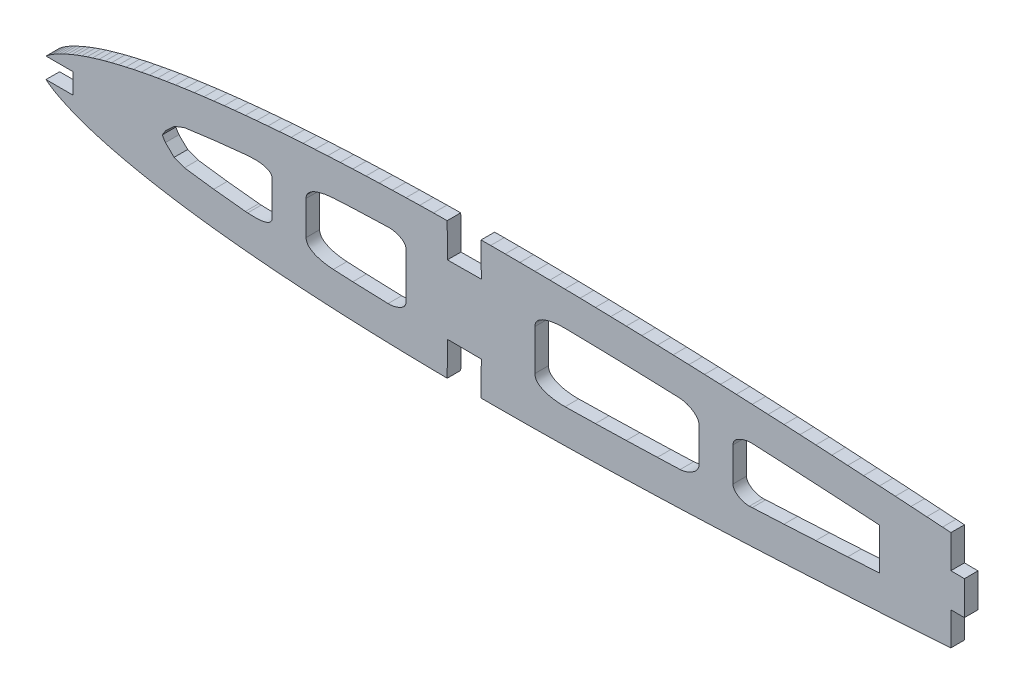
SolidWorks part; units mm, degrees
ref_plane "前视基准面" through (0, 0, 0) normal (0, 0, 1) x (1, 0, 0)
ref_plane "上视基准面" through (0, 0, 0) normal (0, 1, 0) x (1, 0, 0)
ref_plane "右视基准面" through (0, 0, 0) normal (1, 0, 0) x (0, 0, -1)
sketch "Model" plane through (0, 0, 0) normal (0, 0, 1) x (1, 0, 0)
  line L0 (21.4573, -121.0987) -> (25.4497, -121.0987)
  line L1 (25.4497, -121.0987) -> (25.4497, -124.0987)
  line L2 (25.4497, -124.0987) -> (21.4569, -124.0987)
  line L3 (85.6707, -112.4927) -> (85.7057, -117.4927)
  line L4 (85.7057, -117.4927) -> (80.7057, -117.5247)
  line L5 (80.7057, -117.5247) -> (80.6707, -112.5256)
  line L6 (85.6707, -132.7057) -> (85.7037, -127.7057)
  line L7 (85.7037, -127.7057) -> (80.7037, -127.6737)
  line L8 (80.7037, -127.6737) -> (80.6707, -132.6727)
  line L9 (155.0158, -115.2299) -> (153.7727, -115.1437)
  line L10 (153.7727, -115.1437) -> (151.4507, -114.9857)
  line L11 (151.4507, -114.9857) -> (149.1287, -114.8307)
  line L12 (149.1287, -114.8307) -> (146.8067, -114.6807)
  line L13 (146.8067, -114.6807) -> (144.4647, -114.5347)
  line L14 (144.4647, -114.5347) -> (142.1237, -114.3927)
  line L15 (142.1237, -114.3927) -> (139.7817, -114.2547)
  line L16 (139.7817, -114.2547) -> (137.4317, -114.1167)
  line L17 (137.4317, -114.1167) -> (135.0827, -113.9827)
  line L18 (135.0827, -113.9827) -> (132.7327, -113.8527)
  line L19 (132.7327, -113.8527) -> (130.3827, -113.7277)
  line L20 (130.3827, -113.7277) -> (128.0337, -113.6087)
  line L21 (128.0337, -113.6087) -> (125.6837, -113.4957)
  line L22 (125.6837, -113.4957) -> (123.3417, -113.3877)
  line L23 (123.3417, -113.3877) -> (121.0007, -113.2847)
  line L24 (121.0007, -113.2847) -> (118.6587, -113.1877)
  line L25 (118.6587, -113.1877) -> (116.3367, -113.0957)
  line L26 (116.3367, -113.0957) -> (114.0157, -113.0097)
  line L27 (114.0157, -113.0097) -> (111.6927, -112.9297)
  line L28 (111.6927, -112.9297) -> (109.3977, -112.8557)
  line L29 (109.3977, -112.8557) -> (107.1037, -112.7887)
  line L30 (107.1037, -112.7887) -> (104.8077, -112.7277)
  line L31 (104.8077, -112.7277) -> (102.5507, -112.6727)
  line L32 (102.5507, -112.6727) -> (100.2927, -112.6247)
  line L33 (100.2927, -112.6247) -> (98.0347, -112.5837)
  line L34 (98.0347, -112.5837) -> (95.8227, -112.5497)
  line L35 (95.8227, -112.5497) -> (93.6117, -112.5237)
  line L36 (93.6117, -112.5237) -> (91.3997, -112.5047)
  line L37 (91.3997, -112.5047) -> (89.2407, -112.4937)
  line L38 (89.2407, -112.4937) -> (87.0837, -112.4897)
  line L39 (87.0837, -112.4897) -> (85.6707, -112.4927)
  line L40 (41.8937, -120.0317) -> (46.2167, -119.4607)
  line L41 (46.2167, -119.4607) -> (50.8827, -118.9597)
  line L42 (50.8827, -118.9597) -> (51.3585, -118.9186)
  line L43 (63.9417, -118.0316) -> (64.3393, -118.0115)
  line L44 (66.7357, -117.8907) -> (71.9805, -117.7055)
  line L45 (74.5927, -119.2019) -> (74.5927, -124.3091)
  line L46 (71.9424, -127.4906) -> (66.7357, -127.3067)
  line L47 (66.7357, -127.3067) -> (63.8661, -127.1621)
  line L48 (51.2155, -126.2665) -> (50.8827, -126.2377)
  line L49 (50.8827, -126.2377) -> (46.2167, -125.7367)
  line L50 (46.2167, -125.7367) -> (41.8937, -125.1657)
  line L51 (98.0347, -117.5837) -> (101.1763, -117.6456)
  line L52 (103.8714, -117.7064) -> (107.1037, -117.7887)
  line L53 (107.1037, -117.7887) -> (111.6927, -117.9297)
  line L54 (111.6927, -117.9297) -> (114.9886, -118.0475)
  line L55 (125.6837, -118.4957) -> (130.3827, -118.7277)
  line L56 (130.3827, -118.7277) -> (135.0827, -118.9827)
  line L57 (135.0827, -118.9827) -> (139.7817, -119.2547)
  line L58 (139.7817, -119.2547) -> (144.4647, -119.5347)
  line L59 (144.4647, -125.6627) -> (139.7817, -125.9427)
  line L60 (139.7817, -125.9427) -> (135.0827, -126.2147)
  line L61 (135.0827, -126.2147) -> (130.3827, -126.4697)
  line L62 (130.3827, -126.4697) -> (125.6837, -126.7017)
  line L63 (125.6837, -126.7017) -> (125.2777, -126.72)
  line L64 (115.0535, -127.1476) -> (111.6927, -127.2677)
  line L65 (111.6927, -127.2677) -> (107.1037, -127.4087)
  line L66 (107.1037, -127.4087) -> (102.5507, -127.5247)
  line L67 (102.5507, -127.5247) -> (98.0702, -127.613)
  line L68 (41.8937, -120.0317) -> (40.3728, -120.6165)
  line L69 (40.3728, -120.6165) -> (39.0836, -121.8522)
  line L70 (39.0836, -121.8522) -> (38.6143, -122.5987)
  line L71 (41.8937, -125.1657) -> (40.3728, -124.581)
  line L72 (40.3728, -124.581) -> (39.0836, -123.3453)
  line L73 (39.0836, -123.3453) -> (38.6143, -122.5987)
  line L74 (74.5927, -119.2019) -> (74.5927, -125.9956)
  line L75 (93.6117, -119.5956) -> (93.6117, -125.6018)
  line L76 (59.8455, -120.0987) -> (59.8455, -125.0987)
  line L77 (54.8455, -125.0987) -> (54.8455, -120.0987)
  line L78 (122.8505, -120.0987) -> (122.8505, -125.0987)
  line L79 (117.8505, -125.0987) -> (117.8505, -120.0987)
  line L80 (157.0157, -122.5981) -> (157.0157, -120.0981)
  line L81 (157.0157, -122.5981) -> (157.0157, -125.0981)
  line L82 (157.0157, -120.1177) -> (155.0158, -120.0981)
  line L83 (157.0157, -125.0981) -> (155.0157, -125.0981)
  line L84 (155.0157, -125.0981) -> (155.0157, -129.9686)
  line L85 (155.0158, -120.0981) -> (155.0158, -115.2299)
  line L86 (144.4647, -119.5347) -> (144.4647, -125.6627)
  line L87 (101.1763, -117.6456) -> (103.8714, -117.7064)
  line L88 (64.3393, -118.0115) -> (66.7357, -117.8907)
  line L89 (80.6707, -112.5256) -> (78.6397, -112.5517)
  line L90 (78.6397, -112.5517) -> (76.6157, -112.5877)
  line L91 (76.6157, -112.5877) -> (74.5927, -112.6317)
  line L92 (74.5927, -112.6317) -> (72.5697, -112.6847)
  line L93 (72.5697, -112.6847) -> (70.6237, -112.7447)
  line L94 (70.6237, -112.7447) -> (68.6797, -112.8127)
  line L95 (68.6797, -112.8127) -> (66.7357, -112.8907)
  line L96 (66.7357, -112.8907) -> (64.8767, -112.9747)
  line L97 (64.8767, -112.9747) -> (63.0187, -113.0687)
  line L98 (63.0187, -113.0687) -> (61.1617, -113.1717)
  line L99 (61.1617, -113.1717) -> (59.3967, -113.2807)
  line L100 (59.3967, -113.2807) -> (57.6337, -113.3987)
  line L101 (57.6337, -113.3987) -> (55.8707, -113.5287)
  line L102 (55.8707, -113.5287) -> (54.2067, -113.6617)
  line L103 (54.2067, -113.6617) -> (52.5447, -113.8057)
  line L104 (52.5447, -113.8057) -> (50.8827, -113.9597)
  line L105 (50.8827, -113.9597) -> (49.3267, -114.1157)
  line L106 (49.3267, -114.1157) -> (47.7707, -114.2817)
  line L107 (47.7707, -114.2817) -> (46.2167, -114.4607)
  line L108 (46.2167, -114.4607) -> (44.7737, -114.6387)
  line L109 (44.7737, -114.6387) -> (43.3337, -114.8287)
  line L110 (43.3337, -114.8287) -> (41.8937, -115.0317)
  line L111 (41.8937, -115.0317) -> (40.5707, -115.2307)
  line L112 (40.5707, -115.2307) -> (39.2497, -115.4417)
  line L113 (39.2497, -115.4417) -> (37.9307, -115.6667)
  line L114 (37.9307, -115.6667) -> (36.7307, -115.8847)
  line L115 (36.7307, -115.8847) -> (35.5337, -116.1147)
  line L116 (35.5337, -116.1147) -> (34.3397, -116.3607)
  line L117 (34.3397, -116.3607) -> (33.2687, -116.5957)
  line L118 (33.2687, -116.5957) -> (32.2007, -116.8447)
  line L119 (32.2007, -116.8447) -> (31.1367, -117.1087)
  line L120 (31.1367, -117.1087) -> (30.1987, -117.3557)
  line L121 (30.1987, -117.3557) -> (29.2647, -117.6177)
  line L122 (29.2647, -117.6177) -> (28.3347, -117.8967)
  line L123 (28.3347, -117.8967) -> (27.5317, -118.1547)
  line L124 (27.5317, -118.1547) -> (26.7347, -118.4287)
  line L125 (26.7347, -118.4287) -> (25.9447, -118.7227)
  line L126 (25.9447, -118.7227) -> (25.2827, -118.9887)
  line L127 (25.2827, -118.9887) -> (24.6267, -119.2697)
  line L128 (24.6267, -119.2697) -> (23.9777, -119.5677)
  line L129 (23.9777, -119.5677) -> (23.4557, -119.8227)
  line L130 (23.4557, -119.8227) -> (22.9417, -120.0947)
  line L131 (22.9417, -120.0947) -> (22.4397, -120.3897)
  line L132 (22.4397, -120.3897) -> (22.0567, -120.6397)
  line L133 (22.0567, -120.6397) -> (21.6867, -120.9097)
  line L134 (21.6867, -120.9097) -> (21.4573, -121.0987)
  line L135 (85.6707, -132.7057) -> (87.0837, -132.7087)
  line L136 (87.0837, -132.7087) -> (89.2407, -132.7047)
  line L137 (89.2407, -132.7047) -> (91.3997, -132.6937)
  line L138 (91.3997, -132.6937) -> (93.6117, -132.6747)
  line L139 (93.6117, -132.6747) -> (95.8227, -132.6477)
  line L140 (95.8227, -132.6477) -> (98.0347, -132.6147)
  line L141 (98.0347, -132.6147) -> (100.2927, -132.5737)
  line L142 (100.2927, -132.5737) -> (102.5507, -132.5257)
  line L143 (102.5507, -132.5257) -> (104.8077, -132.4707)
  line L144 (104.8077, -132.4707) -> (107.1037, -132.4097)
  line L145 (107.1037, -132.4097) -> (109.3977, -132.3427)
  line L146 (109.3977, -132.3427) -> (111.6927, -132.2687)
  line L147 (111.6927, -132.2687) -> (114.0157, -132.1887)
  line L148 (114.0157, -132.1887) -> (116.3367, -132.1027)
  line L149 (116.3367, -132.1027) -> (118.6587, -132.0107)
  line L150 (118.6587, -132.0107) -> (121.0007, -131.9137)
  line L151 (121.0007, -131.9137) -> (123.3417, -131.8107)
  line L152 (123.3417, -131.8107) -> (125.6837, -131.7027)
  line L153 (125.6837, -131.7027) -> (128.0337, -131.5897)
  line L154 (128.0337, -131.5897) -> (130.3827, -131.4707)
  line L155 (130.3827, -131.4707) -> (132.7327, -131.3457)
  line L156 (132.7327, -131.3457) -> (135.0827, -131.2157)
  line L157 (135.0827, -131.2157) -> (137.4317, -131.0817)
  line L158 (137.4317, -131.0817) -> (139.7817, -130.9437)
  line L159 (139.7817, -130.9437) -> (142.1237, -130.8047)
  line L160 (142.1237, -130.8047) -> (144.4647, -130.6637)
  line L161 (144.4647, -130.6637) -> (146.8067, -130.5177)
  line L162 (146.8067, -130.5177) -> (149.1287, -130.3677)
  line L163 (149.1287, -130.3677) -> (151.4507, -130.2127)
  line L164 (151.4507, -130.2127) -> (153.7727, -130.0547)
  line L165 (153.7727, -130.0547) -> (155.0157, -129.9686)
  line L166 (21.4569, -124.0987) -> (21.6867, -124.2887)
  line L167 (21.6867, -124.2887) -> (22.0567, -124.5587)
  line L168 (22.0567, -124.5587) -> (22.4397, -124.8087)
  line L169 (22.4397, -124.8087) -> (22.9417, -125.1037)
  line L170 (22.9417, -125.1037) -> (23.4557, -125.3757)
  line L171 (23.4557, -125.3757) -> (23.9777, -125.6307)
  line L172 (23.9777, -125.6307) -> (24.6267, -125.9287)
  line L173 (24.6267, -125.9287) -> (25.2827, -126.2097)
  line L174 (25.2827, -126.2097) -> (25.9447, -126.4747)
  line L175 (25.9447, -126.4747) -> (26.7347, -126.7687)
  line L176 (26.7347, -126.7687) -> (27.5317, -127.0437)
  line L177 (27.5317, -127.0437) -> (28.3347, -127.3017)
  line L178 (28.3347, -127.3017) -> (29.2647, -127.5807)
  line L179 (29.2647, -127.5807) -> (30.1987, -127.8427)
  line L180 (30.1987, -127.8427) -> (31.1367, -128.0897)
  line L181 (31.1367, -128.0897) -> (32.2007, -128.3537)
  line L182 (32.2007, -128.3537) -> (33.2687, -128.6027)
  line L183 (33.2687, -128.6027) -> (34.3397, -128.8377)
  line L184 (34.3397, -128.8377) -> (35.5337, -129.0837)
  line L185 (35.5337, -129.0837) -> (36.7307, -129.3137)
  line L186 (36.7307, -129.3137) -> (37.9307, -129.5317)
  line L187 (37.9307, -129.5317) -> (39.2497, -129.7567)
  line L188 (39.2497, -129.7567) -> (40.5707, -129.9677)
  line L189 (40.5707, -129.9677) -> (41.8937, -130.1667)
  line L190 (41.8937, -130.1667) -> (43.3337, -130.3697)
  line L191 (43.3337, -130.3697) -> (44.7737, -130.5597)
  line L192 (44.7737, -130.5597) -> (46.2167, -130.7377)
  line L193 (46.2167, -130.7377) -> (47.7707, -130.9157)
  line L194 (47.7707, -130.9157) -> (49.3267, -131.0827)
  line L195 (49.3267, -131.0827) -> (50.8827, -131.2377)
  line L196 (50.8827, -131.2377) -> (52.5447, -131.3927)
  line L197 (52.5447, -131.3927) -> (54.2067, -131.5367)
  line L198 (54.2067, -131.5367) -> (55.8707, -131.6697)
  line L199 (55.8707, -131.6697) -> (57.6337, -131.7987)
  line L200 (57.6337, -131.7987) -> (59.3967, -131.9177)
  line L201 (59.3967, -131.9177) -> (61.1617, -132.0267)
  line L202 (61.1617, -132.0267) -> (63.0187, -132.1297)
  line L203 (63.0187, -132.1297) -> (64.8767, -132.2237)
  line L204 (64.8767, -132.2237) -> (66.7357, -132.3067)
  line L205 (66.7357, -132.3067) -> (68.6797, -132.3847)
  line L206 (68.6797, -132.3847) -> (70.6237, -132.4537)
  line L207 (70.6237, -132.4537) -> (72.5697, -132.5137)
  line L208 (72.5697, -132.5137) -> (74.5927, -132.5667)
  line L209 (74.5927, -132.5667) -> (76.6157, -132.6107)
  line L210 (76.6157, -132.6107) -> (78.6397, -132.6457)
  line L211 (78.6397, -132.6457) -> (80.6707, -132.6727)
  spline S0 degree 3 poles (71.9805, -117.7055) (72.9834, -117.6701) (74.5927, -118.1984) (74.5927, -119.2019) knots 0 0 0 0 3.010445 3.010445 3.010445 3.010445
  spline S1 degree 3 poles (71.9424, -127.4906) (72.9561, -127.5264) (74.5927, -127.0099) (74.5927, -125.9956) knots 0 0 0 0 3.04286 3.04286 3.04286 3.04286
  spline S2 degree 3 poles (98.0347, -117.5837) (96.4154, -117.5518) (93.6117, -117.9759) (93.6117, -119.5956) knots 0 0 0 0 4.859072 4.859072 4.859072 4.859072
  spline S3 degree 3 poles (93.6117, -125.6018) (93.6117, -127.2322) (96.4401, -127.6452) (98.0702, -127.613) knots 0 0 0 0 4.891062 4.891062 4.891062 4.891062
  spline S4 degree 3 poles (51.3585, -118.9186) (52.5811, -118.813) (54.8455, -118.8717) (54.8455, -120.0987) knots 0 0 0 0 3.681245 3.681245 3.681245 3.681245
  spline S5 degree 3 poles (51.2155, -126.2665) (52.4819, -126.3759) (54.8455, -126.3698) (54.8455, -125.0987) knots 0 0 0 0 3.813194 3.813194 3.813194 3.813194
  spline S6 degree 3 poles (63.9417, -118.0316) (62.4142, -118.1086) (59.8455, -118.5693) (59.8455, -120.0987) knots 0 0 0 0 4.588218 4.588218 4.588218 4.588218
  spline S7 degree 3 poles (59.8455, -125.0987) (59.8455, -126.6051) (62.3616, -127.0862) (63.8661, -127.1621) knots 0 0 0 0 4.519147 4.519147 4.519147 4.519147
  spline S8 degree 3 poles (114.9886, -118.0475) (116.1615, -118.0895) (117.8505, -118.925) (117.8505, -120.0987) knots 0 0 0 0 3.521084 3.521084 3.521084 3.521084
  spline S9 degree 3 poles (115.0535, -127.1476) (116.2085, -127.1063) (117.8505, -126.2545) (117.8505, -125.0987) knots 0 0 0 0 3.467184 3.467184 3.467184 3.467184
  spline S10 degree 3 poles (125.6837, -118.4957) (124.6, -118.4422) (122.8505, -119.0137) (122.8505, -120.0987) knots 0 0 0 0 3.255252 3.255252 3.255252 3.255252
  spline S11 degree 3 poles (122.8505, -125.0987) (122.8505, -126.0717) (124.3057, -126.7638) (125.2777, -126.72) knots 0 0 0 0 2.918848 2.918848 2.918848 2.918848
extrude "凸台-拉伸1" add sketch "Model" along normal blind 2 contours L210 L211 L8 L7 L6 L135 L136 L137 L138 L139 L140 L141 L142 L143 L144 L145 L146 L147 L148 L149 L150 L151 L152 L153 L154 L155 L156 L157 L158 L159 L160 L161 L162 L163 L164 L165 L84 L83 L81 L80 L82 L85 L9 L10 L11 L12 L13 L14 L15 L16 L17 region at (91.1156, -122.5991, 0)
